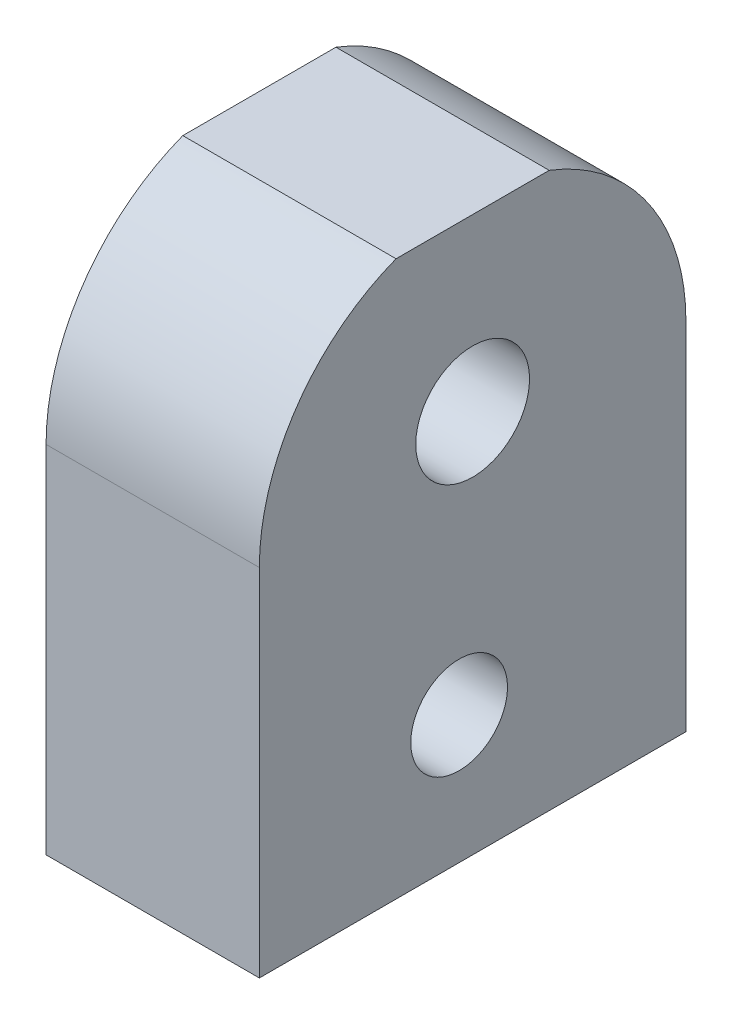
SolidWorks part; units mm, degrees
ref_plane "Front Plane" through (0, 0, 0) normal (0, 0, 1) x (1, 0, 0)
ref_plane "Top Plane" through (0, 0, 0) normal (0, 1, 0) x (1, 0, 0)
ref_plane "Right Plane" through (0, 0, 0) normal (1, 0, 0) x (0, 0, -1)
other "Configuration Table"
sketch "草图1" plane through (0, 0, 0) normal (0, 1, 0) x (1, 0, 0)
  line L0 (0, 0) -> (0, -30)
  line L1 (0, 0) -> (15, 0)
  line L2 (15, 0) -> (15, -30)
  line L3 (15, -30) -> (0, -30)
extrude "凸台-拉伸1" add sketch "草图1" along normal blind 25
sketch "草图3" plane through (0, 0, 0) normal (-1, 0, 0) x (0, 0, 1)
  line L0 (15, 25) -> (15, 0) construction
  line L1 (0, 25) -> (30, 25) construction
  line L2 (0, 0) -> (30, 0) construction
  line L7 (0, 25) -> (30, 25)
  circle A2 centre (15, 25) radius 15
  line M7 (30, 25) -> (0, 25)
  dimension "D1" = 0
extrude "凸台-拉伸3" add sketch "草图3" against normal blind 15 contours A2 L7 M7 region at (0, 31.3662, 15)
sketch "草图4" plane through (0, 0, 0) normal (0, -1, 0) x (1, 0, 0)
  line L0 (7.5, 30) -> (7.5, 0) construction
  line L1 (15, 30) -> (0, 30) construction
  line L2 (0, 0) -> (15, 0) construction
  circle A1 centre (7.5, 24) radius 1.65
  circle A2 centre (7.5, 6) radius 1.65
  dimension "D1" = 6
  dimension "D2" = 6
extrude "切除-拉伸2" cut sketch "草图4" against normal blind 10 contours L0 A1 | A1 L0 | L0 A2 | A2 L0 region at (8.2003, 0, 24) region at (8.2003, 0, 6) region at (6.7997, 0, 6) region at (6.7997, 0, 24)
sketch "草图5" plane through (0, 0, 0) normal (-1, 0, 0) x (0, 0, 1)
  line L0 (0, 0) -> (30, 0) construction
  line L2 (0, 25) -> (0, 0) construction
  circle A0 centre (15.95, 9) radius 3.4
  dimension "D2" = 6.8
  dimension "D1" = 9
  dimension "D3" = 15.95
sketch "草图9" plane through (0, 0, 0) normal (-1, 0, 0) x (0, 0, 1)
  line L0 (15, 27) -> (15, 40) construction
  circle A0 centre (15, 27) radius 6.1
  arc A1 (30, 25) -> (0, 25) centre (15, 25) ccw construction
  dimension "D1" = 12.2
extrude "切除-拉伸3" cut sketch "草图9" against normal blind 6
sketch "草图10" plane through (6, 0, 0) normal (-1, 0, 0) x (0, 0, 1)
  circle A0 centre (15, 27) radius 4
  dimension "D1" = 8
extrude "切除-拉伸4" cut sketch "草图10" against normal through all contours A0
sketch "草图12" plane through (0, 0, 0) normal (-1, 0, 0) x (0, 0, 1)
  line L0 (15, 39) -> (15, 25) construction
  line L1 (9.6148, 39) -> (20.3852, 39)
  arc A1 (30, 25) -> (0, 25) centre (15, 25) ccw construction
  point P9 (15, 39)
  arc M7 (30, 25) -> (0, 25) centre (15, 25) ccw
extrude "切除-拉伸6" cut sketch "草图12" against normal through all and the other way through all contours L1 M7 region at (0, 39.4012, 15)
extrude "切除-拉伸7" cut sketch "草图5" against normal through all
